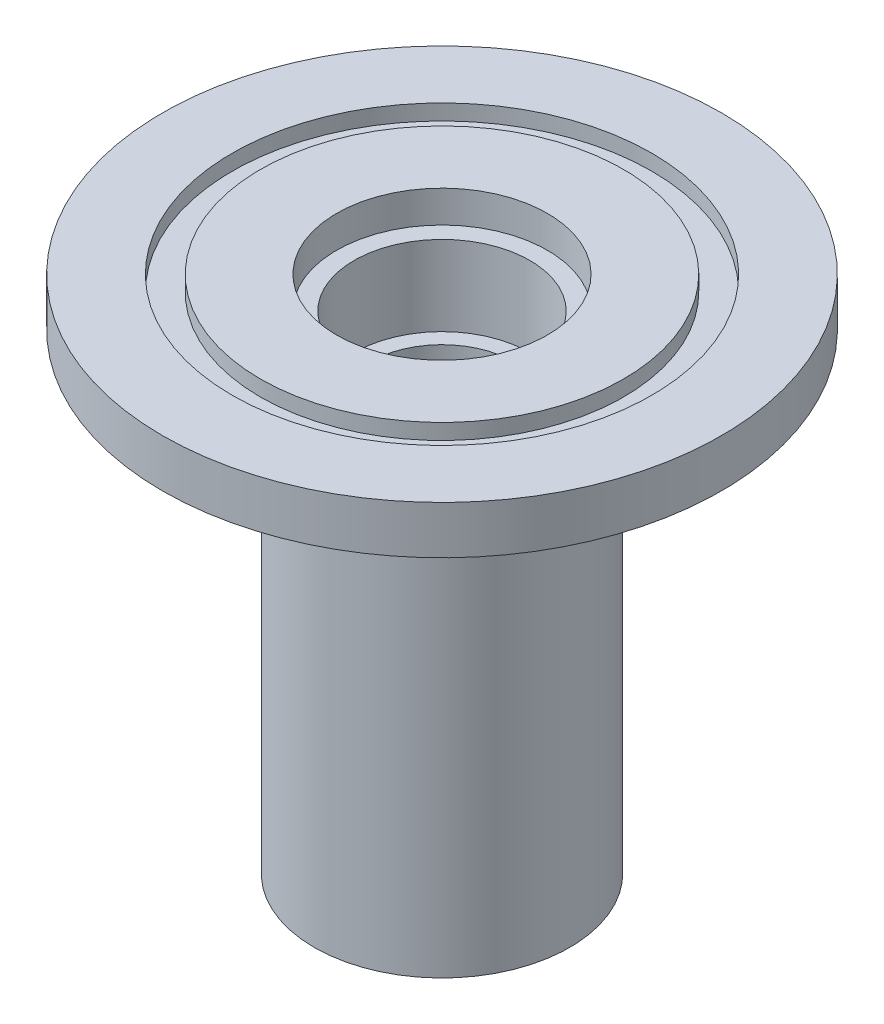
SolidWorks part; units mm, degrees
ref_plane "Front Plane" through (0, 0, 0) normal (0, 0, 1) x (1, 0, 0)
ref_plane "Top Plane" through (0, 0, 0) normal (0, 1, 0) x (1, 0, 0)
ref_plane "Right Plane" through (0, 0, 0) normal (1, 0, 0) x (0, 0, -1)
sketch "Sketch1" plane through (0, 0, 0) normal (0, 0, 1) x (1, 0, 0)
  line L0 (0, 0) -> (0, -122.9972) construction
  line L1 (35, 0) -> (26.2636, 0)
  line L2 (13.2, 0) -> (13.2, -4)
  line L3 (13.2, -4) -> (11, -4)
  line L4 (11, -4) -> (11, -14)
  line L9 (12.5, -65) -> (16, -65)
  line L10 (16, -65) -> (16, -6)
  line L11 (16, -6) -> (35, -6)
  line L12 (35, -6) -> (35, 0)
  line L23 (22.733, 0) -> (22.733, -1.9558)
  line L24 (22.733, -1.9558) -> (26.2636, -1.9558)
  line L25 (26.2636, -1.9558) -> (26.2636, 0)
  line L26 (22.733, 0) -> (13.2, 0)
  line L27 (11, -14) -> (9, -14)
  line L28 (9, -14) -> (9, -17)
  line L29 (9, -17) -> (11, -17)
  line L30 (11, -17) -> (11, -30.5)
  line L31 (12.5, -65) -> (12.5, -30.5)
  line L32 (12.5, -30.5) -> (11, -30.5)
  dimension "D1" = 22
  dimension "D2" = 26.4
  dimension "D3" = 4
  dimension "D4" = 18
  dimension "D5" = 14
  dimension "D6" = 3
  dimension "D7" = 25
  dimension "D8" = 65
  dimension "D9" = 6
  dimension "D10" = 32
  dimension "D11" = 70
  dimension "D12" = 52.5272
  dimension "D13" = 1.9558
  dimension "D14" = 3.5306
  dimension "D15" = 13.5
revolve "Revolve1" add sketch "Sketch1" angle 360 about L0
